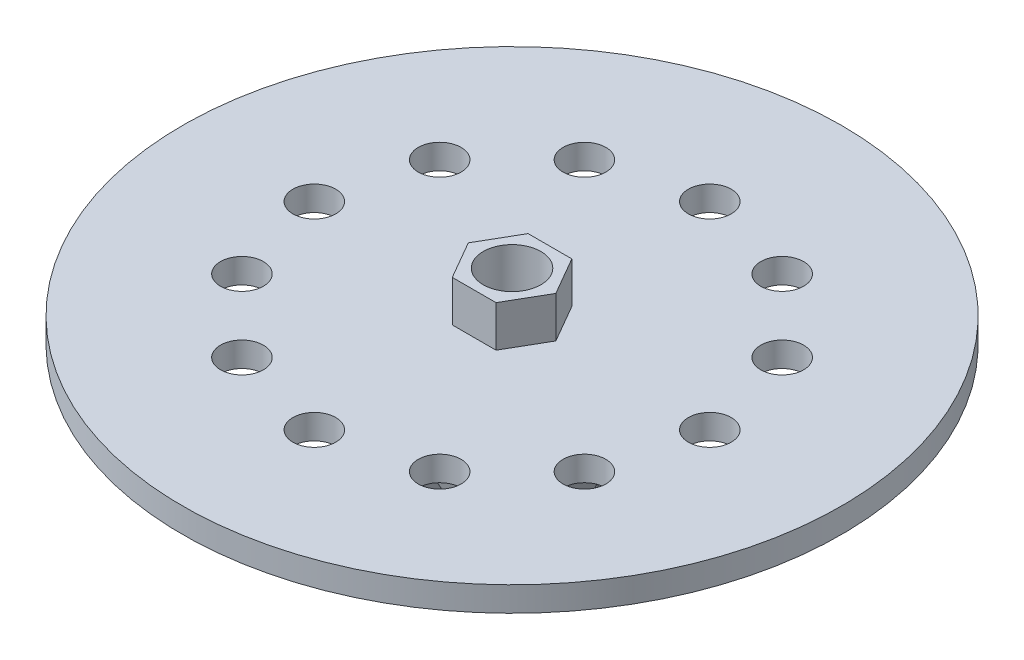
SolidWorks part; units mm, degrees
ref_plane "Front Plane" through (0, 0, 0) normal (0, 0, 1) x (1, 0, 0)
ref_plane "Top Plane" through (0, 0, 0) normal (0, 1, 0) x (1, 0, 0)
ref_plane "Right Plane" through (0, 0, 0) normal (1, 0, 0) x (0, 0, -1)
sketch "Sketch1" plane through (0, 0, 0) normal (0, 1, 0) x (1, 0, 0)
  circle A0 centre (0, 0) radius 50.8
  dimension "D1" = 101.6
extrude "Boss-Extrude1" add sketch "Sketch1" along normal blind 3.81
sketch "Sketch4" plane through (0, 3.81, 0) normal (0, 1, 0) x (1, 0, 0)
  line L0 (-3.3729, 5.842) -> (3.3729, 5.842)
  line L1 (3.3729, 5.842) -> (6.7458, 0)
  line L2 (6.7458, 0) -> (3.3729, -5.842)
  line L3 (3.3729, -5.842) -> (-3.3729, -5.842)
  line L4 (-3.3729, -5.842) -> (-6.7458, 0)
  line L5 (-6.7458, 0) -> (-3.3729, 5.842)
  circle A0 centre (0, 0) radius 4.445
  point P6 (0, 5.842)
  dimension "D3" = 8.89
  dimension "D1" = 120
  dimension "D2" = 11.684
extrude "Boss-Extrude2" add sketch "Sketch4" along normal blind 6.35 contours L5 L4 L3 L2 L1 L0 A0 region at (0, 3.81, -5.6635)
sketch "Sketch5" plane through (0, 3.81, 0) normal (0, 1, 0) x (1, 0, 0)
  circle A0 centre (0, 30.48) radius 3.302
  circle A1 centre (15.24, 26.3965) radius 3.302
  circle A2 centre (26.3965, 15.24) radius 3.302
  circle A3 centre (30.48, 0) radius 3.302
  circle A4 centre (26.3965, -15.24) radius 3.302
  circle A5 centre (15.24, -26.3965) radius 3.302
  circle A6 centre (0, -30.48) radius 3.302
  circle A7 centre (-15.24, -26.3965) radius 3.302
  circle A8 centre (-26.3965, -15.24) radius 3.302
  circle A9 centre (-30.48, 0) radius 3.302
  circle A10 centre (-26.3965, 15.24) radius 3.302
  circle A11 centre (-15.24, 26.3965) radius 3.302
  point P28 (0, 0)
  dimension "D2" = 6.604
  dimension "D1" = 30.48
extrude "Cut-Extrude1" cut sketch "Sketch5" against normal through all
sketch "Sketch6" plane through (0, 0, 0) normal (0, -1, 0) x (1, 0, 0)
  circle A0 centre (0, 0) radius 3.2639
  circle A1 centre (0, 0) radius 9.525
  dimension "D1" = 6.5278
  dimension "D2" = 19.05
extrude "Boss-Extrude3" add sketch "Sketch6" along normal blind 17.78 contours A1 A0 region at (-9.2556, 0, 0)
sketch "Sketch7" plane through (0, 0, 0) normal (0, -1, 0) x (1, 0, 0)
  line L2 (-3.2639, 0) -> (-3.2639, 20.32)
  line L3 (-3.2639, 20.32) -> (3.2639, 20.32)
  line L4 (3.2639, 0) -> (3.2639, 20.32)
  circle A0 centre (0, 0) radius 3.2639 construction
  arc A1 (3.2639, 0) -> (-3.2639, 0) centre (0, 0) ccw
  circle A2 centre (0, 0) radius 3.2639 construction
  dimension "D1" = 20.32
extrude "Boss-Extrude4" add sketch "Sketch7" along normal up to surface (17.78 mm away) up to face at (0, -17.78, -3.2639)
chamfer "Chamfer1" distance 10.16 angle 61 1 edges at (0, -17.78, 20.32) first distance on face at (0, -17.78, -3.2639)
pattern_circular "CirPattern1" count 5 over 360 about axis through (0, -17.78, 0) along (0, 1, 0) of "Boss-Extrude4", "Chamfer1" reverse direction yes
